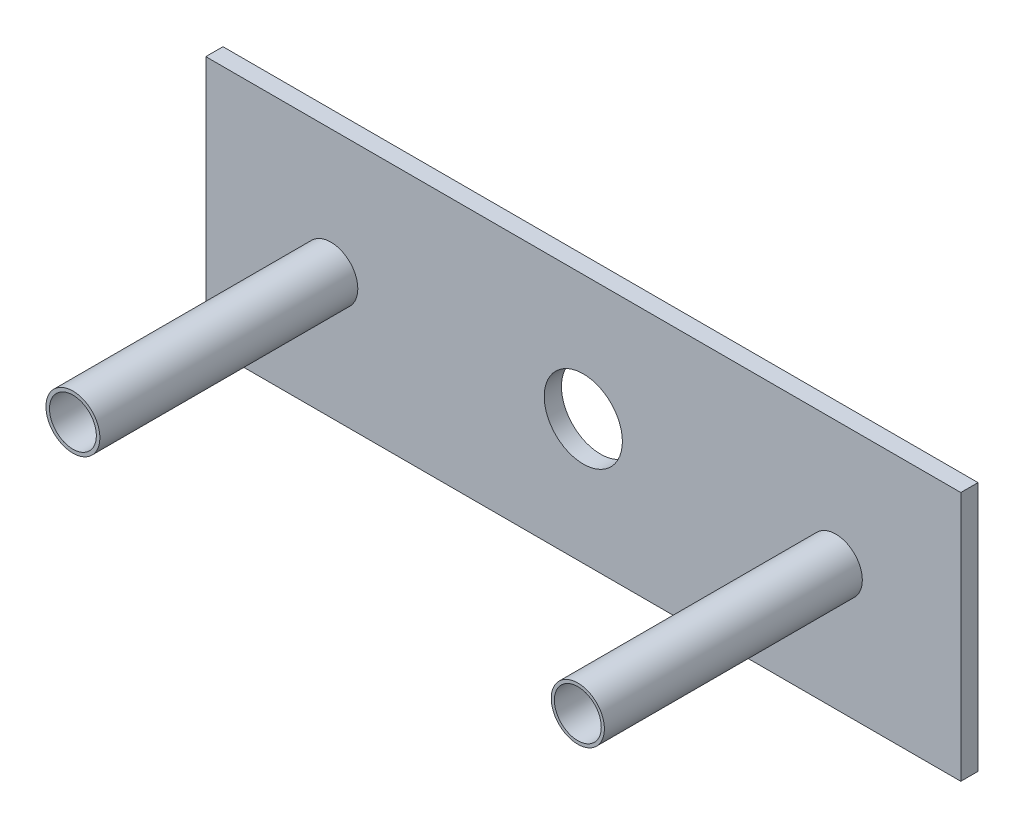
SolidWorks part; units mm, degrees
ref_plane "Plan de face" through (0, 0, 0) normal (0, 0, 1) x (1, 0, 0)
ref_plane "Plan de dessus" through (0, 0, 0) normal (0, 1, 0) x (1, 0, 0)
ref_plane "Plan de droite" through (0, 0, 0) normal (1, 0, 0) x (0, 0, -1)
sketch "Esquisse1" plane through (0, 0, 0) normal (0, 0, 1) x (1, 0, 0)
  line L1 (-47.6288, 18.2599) -> (48.9712, 18.2599)
  line L2 (-47.6288, 18.2599) -> (-47.6288, -13.7401)
  line L3 (-47.6288, -13.7401) -> (48.9712, -13.7401)
  line L4 (48.9712, 18.2599) -> (48.9712, -13.7401)
  dimension "D1" = 96.6
  dimension "D2" = 32
extrude "Boss.-Extru.1" add sketch "Esquisse1" along normal blind 2.2
sketch "Esquisse6" plane through (0, 0, 2.2) normal (0, 0, 1) x (1, 0, 0)
  line L0 (-47.6288, 18.2599) -> (-47.6288, -13.7401) construction
  line L3 (48.9712, 18.2599) -> (-47.6288, 18.2599) construction
  line L4 (48.9712, -13.7401) -> (48.9712, 18.2599) construction
  circle A0 centre (-31.6288, 2.2599) radius 3.45
  circle A1 centre (32.9712, 2.2599) radius 3.4
  dimension "D1" = 6.9
  dimension "D4" = 6.8
  dimension "D2" = 16
  dimension "D3" = 16
  dimension "D5" = 16
  dimension "D6" = 16
extrude "Boss.-Extru.2" add sketch "Esquisse6" along normal blind 33
sketch "Esquisse7" plane through (0, 0, 35.2) normal (0, 0, 1) x (1, 0, 0)
  line L1 (-47.6288, 18.2599) -> (-47.6288, -13.7401) construction
  line L3 (48.9712, 18.2599) -> (-47.6288, 18.2599) construction
  line L4 (48.9712, -13.7401) -> (48.9712, 18.2599) construction
  line L5 (-47.6288, -13.7401) -> (48.9712, -13.7401) construction
  circle A0 centre (-31.6288, 2.2599) radius 3
  circle A1 centre (32.9712, 2.2599) radius 3
  circle A2 centre (0.6712, 2.2599) radius 5
  dimension "D1" = 6
  dimension "D4" = 6
  dimension "D7" = 10
  dimension "D2" = 16
  dimension "D3" = 16
  dimension "D5" = 16
  dimension "D6" = 16
  dimension "D8" = 16
  dimension "D9" = 48.3
extrude "Enlèv. mat.-Extru.1" cut sketch "Esquisse7" against normal through all
